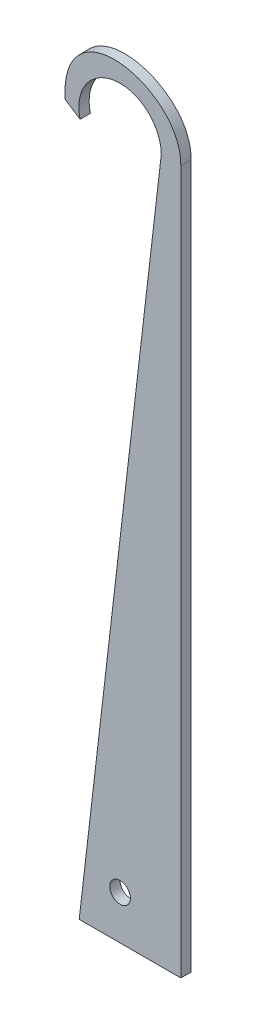
SolidWorks part; units mm, degrees
ref_plane "Front Plane" through (0, 0, 0) normal (0, 0, 1) x (1, 0, 0)
ref_plane "Top Plane" through (0, 0, 0) normal (0, 1, 0) x (1, 0, 0)
ref_plane "Right Plane" through (0, 0, 0) normal (1, 0, 0) x (0, 0, -1)
sketch "Sketch1" plane through (0, 0, 0) normal (0, 0, 1) x (1, 0, 0)
  line L1 (0, 0) -> (0, -406.4) construction
  line L2 (25.4, 0) -> (-25.1733, -433.3868)
  line L4 (37.4288, -433.3868) -> (37.4288, 0)
  line L5 (-24.6361, -6.1823) -> (-33.983, 0)
  line L6 (-25.1733, -433.3868) -> (37.4288, -433.3868)
  circle A0 centre (0, 0) radius 25.4 construction
  arc A1 (-25.4, 0) -> (25.4, 0) centre (0, 0) cw
  circle A2 centre (0, -406.4) radius 6.35
  arc A3 (-25.4, 0) -> (-24.6361, -6.1823) centre (0, 0) ccw
  spline S0 degree 3 poles (-33.983, 0) (-36.5167, 56.1179) (38.1207, 39.9844) (37.4288, 0) knots 0 0 0 0 1 1 1 1
  dimension "D1" = 50.8
  dimension "D2" = 406.4
  dimension "D3" = 12.7
extrude "Boss-Extrude1" add sketch "Sketch1" along normal blind 6.35 contours S0 L5 A3 A1 L2 L6 L4 A2 region at (15.0111, -246.4245, 0)
